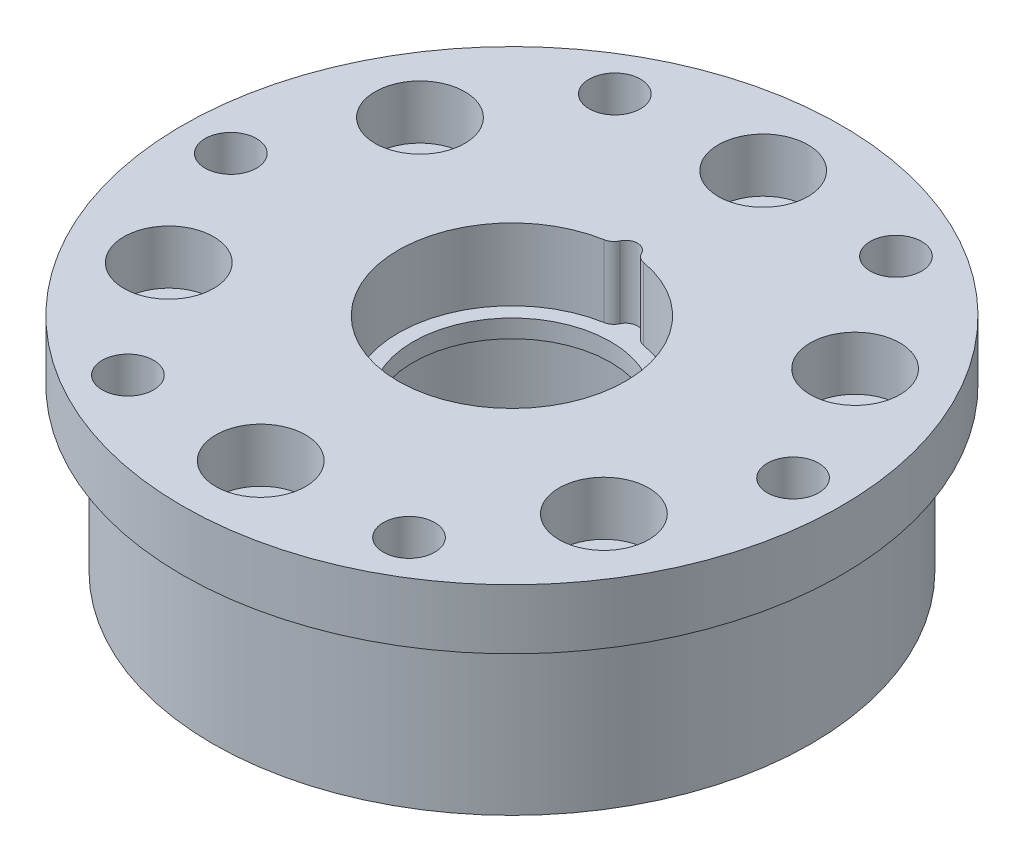
SolidWorks part; units mm, degrees
ref_plane "Front Plane" through (0, 0, 0) normal (0, 0, 1) x (1, 0, 0)
ref_plane "Top Plane" through (0, 0, 0) normal (0, 1, 0) x (1, 0, 0)
ref_plane "Right Plane" through (0, 0, 0) normal (1, 0, 0) x (0, 0, -1)
sketch "Sketch1" plane through (0, 0, 0) normal (0, 1, 0) x (1, 0, 0)
  circle A0 centre (0, 0) radius 21 construction
  circle A1 centre (0, 21) radius 2.5
  circle A2 centre (18.1865, 10.5) radius 2.5
  circle A3 centre (18.1865, -10.5) radius 2.5
  circle A4 centre (0, -21) radius 2.5
  circle A5 centre (-18.1865, -10.5) radius 2.5
  circle A6 centre (-18.1865, 10.5) radius 2.5
  circle A7 centre (0, 0) radius 25
  circle A8 centre (0, 0) radius 8.25
  point P18 (0, 0)
  dimension "D1" = 42
  dimension "D2" = 5
  dimension "D4" = 50
  dimension "D5" = 16.5
  dimension "D3" = 6
extrude "Boss-Extrude1" add sketch "Sketch1" along normal blind 10
sketch "Sketch2" plane through (0, 10, 0) normal (0, 1, 0) x (1, 0, 0)
  circle A0 centre (0, 0) radius 9.5
  circle A1 centre (0, 0) radius 15.5
  dimension "D1" = 19
  dimension "D2" = 6
extrude "Boss-Extrude2" add sketch "Sketch2" along normal blind 8.5
sketch "Sketch4" plane through (0, 10, 0) normal (0, 1, 0) x (1, 0, 0)
  circle A0 centre (0, 0) radius 9.5 construction
  circle A1 centre (0, 0) radius 8.25 construction
  circle A2 centre (0, 0) radius 9.5
  circle A3 centre (0, 0) radius 8.25
extrude "Boss-Extrude3" add sketch "Sketch4" along normal blind 2.5
sketch "Sketch3" plane through (0, 0, 0) normal (0, -1, 0) x (1, 0, 0)
  circle A0 centre (0, 0) radius 12.5
  dimension "D1" = 25
extrude "Cut-Extrude1" cut sketch "Sketch3" against normal blind 11
chamfer "Chamfer1" distance 2.5 angle 45 1 edges at (0, 11, -12.5)
sketch "Sketch5" plane through (0, 10, 0) normal (0, 1, 0) x (1, 0, 0)
  circle A0 centre (0, 21) radius 3.75
  circle A1 centre (18.1865, 10.5) radius 3.75
  circle A2 centre (18.1865, -10.5) radius 3.75
  circle A3 centre (0, -21) radius 3.75
  circle A4 centre (-18.1865, -10.5) radius 3.75
  circle A5 centre (-18.1865, 10.5) radius 3.75
  circle A6 centre (0, 0) radius 25 construction
  circle A7 centre (0, 0) radius 25
  circle A8 centre (0, 0) radius 15.5 construction
  circle A9 centre (0, 0) radius 15.5
  point P15 (0, 0)
  dimension "D1" = 7.5
  dimension "D2" = 6
extrude "Boss-Extrude4" add sketch "Sketch5" along normal blind 8.5
sketch "Sketch6" plane through (0, 18.5, 0) normal (0, 1, 0) x (1, 0, 0)
  circle A0 centre (0, 0) radius 25 construction
  circle A1 centre (0, 0) radius 25
  circle A2 centre (0, 0) radius 27.55
  dimension "D1" = 55.1
extrude "Boss-Extrude5" add sketch "Sketch6" against normal blind 5
sketch "Sketch7" plane through (0, 10, 0) normal (0, 1, 0) x (1, 0, 0)
  circle A0 centre (18.1865, -10.5) radius 3.75 construction
  circle A1 centre (0, -21) radius 3.75 construction
  circle A2 centre (-18.1865, -10.5) radius 3.75 construction
  circle A3 centre (-18.1865, 10.5) radius 3.75 construction
  circle A4 centre (0, 21) radius 3.75 construction
  circle A5 centre (18.1865, 10.5) radius 3.75 construction
  circle A6 centre (18.1865, -10.5) radius 3.75
  circle A7 centre (0, -21) radius 3.75
  circle A8 centre (-18.1865, -10.5) radius 3.75
  circle A9 centre (-18.1865, 10.5) radius 3.75
  circle A10 centre (0, 21) radius 3.75
  circle A11 centre (18.1865, 10.5) radius 3.75
  circle A12 centre (-18.1865, -10.5) radius 2.5 construction
  circle A13 centre (0, -21) radius 2.5 construction
  circle A14 centre (18.1865, -10.5) radius 2.5 construction
  circle A15 centre (18.1865, 10.5) radius 2.5 construction
  circle A16 centre (0, 21) radius 2.5 construction
  circle A17 centre (-18.1865, 10.5) radius 2.5 construction
  circle A18 centre (-18.1865, -10.5) radius 2.5
  circle A19 centre (0, -21) radius 2.5
  circle A20 centre (18.1865, -10.5) radius 2.5
  circle A21 centre (18.1865, 10.5) radius 2.5
  circle A22 centre (0, 21) radius 2.5
  circle A23 centre (-18.1865, 10.5) radius 2.5
extrude "Boss-Extrude6" add sketch "Sketch7" along normal blind 4
sketch "Sketch8" plane through (0, 18.5, 0) normal (0, 1, 0) x (1, 0, 0)
  circle A0 centre (0, 9.5) radius 1
  circle A1 centre (0, 0) radius 9.5 construction
  circle A2 centre (0, 0) radius 9.5 construction
  dimension "D1" = 2
extrude "Cut-Extrude2" cut sketch "Sketch8" against normal up to surface (6 mm away) up to face at (0, 12.5, 9.5)
fillet "Fillet1" radius 1 2 edges at (0.9986, 15.5, -9.4474) (-0.9986, 15.5, -9.4474)
sketch "Sketch11" plane through (0, 18.5, 0) normal (0, 1, 0) x (1, 0, 0)
  line L0 (0, 0) -> (17.55, 30.3975) construction
  circle A0 centre (0, 0) radius 23.5 construction
  circle A1 centre (11.75, 20.3516) radius 2.15
  circle A2 centre (23.5, 0) radius 2.15
  circle A3 centre (11.75, -20.3516) radius 2.15
  circle A4 centre (-11.75, -20.3516) radius 2.15
  circle A5 centre (-23.5, 0) radius 2.15
  circle A6 centre (-11.75, 20.3516) radius 2.15
  point P18 (0, 0)
  dimension "D2" = 47
  dimension "D3" = 4.3
  dimension "D1" = 60
  dimension "D4" = 6
extrude "Cut-Extrude3" cut sketch "Sketch11" against normal blind 4.8
